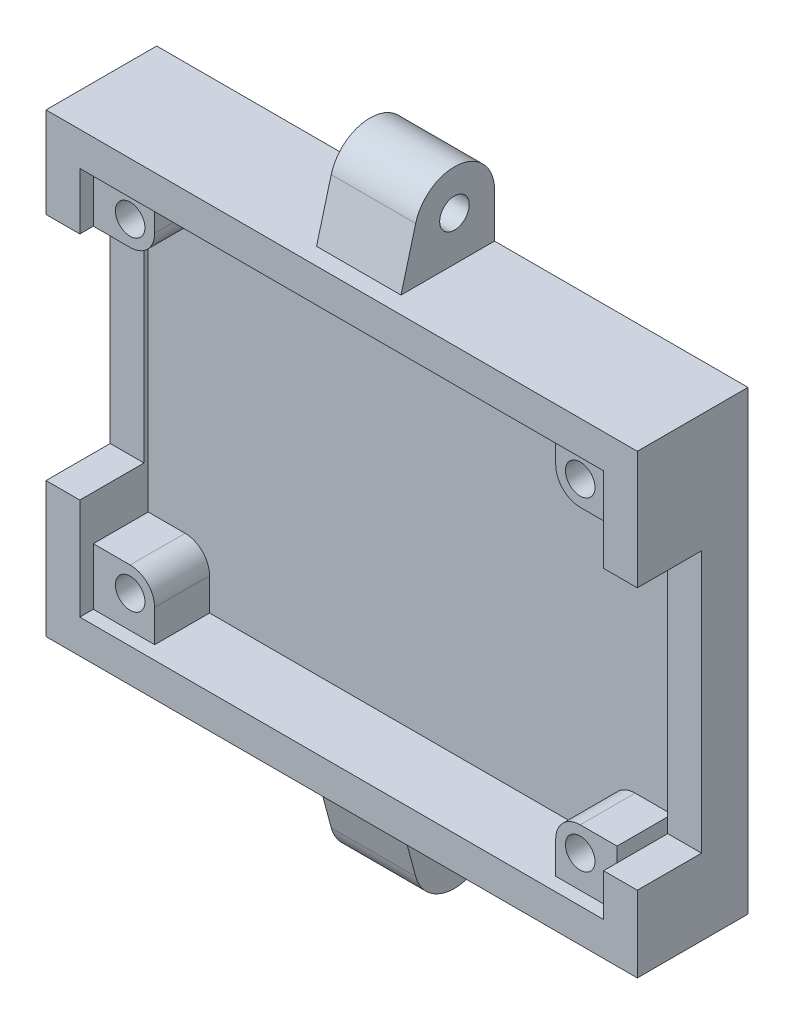
SolidWorks part; units mm, degrees
ref_plane "Front Plane" through (0, 0, 0) normal (0, 0, 1) x (1, 0, 0)
ref_plane "Top Plane" through (0, 0, 0) normal (0, 1, 0) x (1, 0, 0)
ref_plane "Right Plane" through (0, 0, 0) normal (1, 0, 0) x (0, 0, -1)
sketch "Sketch1" plane through (0, 0, 0) normal (0, 0, 1) x (1, 0, 0)
  line L0 (0, -55) -> (0, 55) construction
  line L1 (-31, -23) -> (31, -23)
  line L2 (-31, -23) -> (-31, 23)
  line L3 (-31, 23) -> (31, 23)
  line L4 (31, -23) -> (31, 23)
  line L5 (-31, -23) -> (31, 23) construction
  line L6 (-31, 23) -> (31, -23) construction
  line L7 (55, 0) -> (-55, 0) construction
  line L8 (-35, -27) -> (-35, 27)
  line L9 (-35, 27) -> (35, 27)
  line L10 (35, -27) -> (35, 27)
  line L11 (-35, -27) -> (35, -27)
  circle A0 centre (-26.6383, 19.175) radius 1.75
  circle A1 centre (26.6383, 19.175) radius 1.75
  circle A2 centre (-26.6383, -19.175) radius 1.75
  circle A3 centre (26.6383, -19.175) radius 1.75
  point P0 (0, 0)
  dimension "D1" = 53.2767
  dimension "D5" = 3.5
  dimension "D2" = 38.35
  dimension "D3" = 62
  dimension "D4" = 46
  dimension "D6" = 4
extrude "Boss-Extrude1" add sketch "Sketch1" along normal blind 5 contours L1 L4 L3 L2 A3 A1 A0 A2 region at (0, 0, 0)
extrude "Boss-Extrude2" add sketch "Sketch1<3>" along normal offset from surface (13.1 mm away) 8.1 contours L8 L11 L10 L9 L4 L1 L2 L3 region at (-34.1159, 0, 0) up to face at (28.3883, -19.175, 5) offset beyond the face yes
sketch "Sketch1<3>" plane through (0, 0, 0) normal (0, 0, 1) x (1, 0, 0) same geometry as "Sketch1"
sketch "Sketch2" plane through (0, 0, 5) normal (0, 0, 1) x (1, 0, 0)
  line L1 (-9.8333, 23) -> (2.8667, 23)
  line L2 (-9.8333, 23) -> (-9.8333, 19)
  line L3 (-9.8333, 19) -> (2.8667, 19)
  line L4 (2.8667, 23) -> (2.8667, 19)
  line L7 (-31, 23) -> (31, 23) construction
  line L8 (-31, -23) -> (-31, 23) construction
  point P4 (-8.8333, 22.25)
  dimension "D1" = 4
  dimension "D2" = 12.7
  dimension "D3" = 21.1667
extrude "Cut-Extrude1" cut sketch "Sketch2" against normal blind 4
sketch "Sketch3" plane through (0, 0, 5) normal (0, 0, 1) x (1, 0, 0)
  line L0 (-23.7383, 19.175) -> (-23.7383, 23)
  line L1 (-31, 23) -> (-9.8333, 23) construction
  line L2 (-23.7383, 23) -> (-31, 23)
  line L3 (-31, 23) -> (-31, 16.275)
  line L4 (-31, -23) -> (-31, 23) construction
  line L5 (-31, 16.275) -> (-26.6383, 16.275)
  line L7 (55, 0) -> (-55, 0) construction
  line L8 (-31, -16.275) -> (-26.6383, -16.275)
  line L9 (-31, -23) -> (-31, -16.275)
  line L10 (-23.7383, -23) -> (-31, -23)
  line L11 (-23.7383, -19.175) -> (-23.7383, -23)
  line L12 (0, -55) -> (0, 55) construction
  line L13 (31, -23) -> (31, -16.275)
  line L14 (23.7383, -23) -> (31, -23)
  line L15 (23.7383, -19.175) -> (23.7383, -23)
  line L16 (31, -16.275) -> (26.6383, -16.275)
  line L17 (31, 16.275) -> (26.6383, 16.275)
  line L18 (31, 23) -> (31, 16.275)
  line L19 (23.7383, 23) -> (31, 23)
  line L20 (23.7383, 19.175) -> (23.7383, 23)
  arc A0 (-26.6383, 16.275) -> (-23.7383, 19.175) centre (-26.6383, 19.175) ccw
  arc A4 (-26.6383, -16.275) -> (-23.7383, -19.175) centre (-26.6383, -19.175) cw
  arc A5 (26.6383, -16.275) -> (23.7383, -19.175) centre (26.6383, -19.175) ccw
  arc A6 (26.6383, 16.275) -> (23.7383, 19.175) centre (26.6383, 19.175) cw
  circle A7 centre (-26.6383, -19.175) radius 1.75 construction
  circle A8 centre (26.6383, -19.175) radius 1.75 construction
  circle A9 centre (26.6383, 19.175) radius 1.75 construction
  circle A10 centre (-26.6383, 19.175) radius 1.75 construction
  circle A11 centre (-26.6383, -19.175) radius 1.75
  circle A12 centre (26.6383, -19.175) radius 1.75
  circle A13 centre (26.6383, 19.175) radius 1.75
  circle A14 centre (-26.6383, 19.175) radius 1.75
  dimension "D1" = 5.8
extrude "Boss-Extrude3" add sketch "Sketch3" along normal blind 6.5
sketch "Sketch4" plane through (0, 0, 13.1) normal (0, 0, 1) x (1, 0, 0)
  line L0 (-35, -27) -> (-35, 27) construction
  line L1 (-31, 16.275) -> (-35, 16.275)
  line L2 (-31, 16.275) -> (-31, -11)
  line L3 (-31, -11) -> (-35, -11)
  line L4 (-35, 16.275) -> (-35, -11)
  line L11 (-23.7383, 23) -> (-31, 23) construction
  line L12 (31, -16.275) -> (31, 16.275) construction
  line L13 (31, -18) -> (35, -18)
  line L14 (31, -18) -> (31, 13)
  line L15 (31, 13) -> (35, 13)
  line L16 (35, -18) -> (35, 13)
  line L17 (35, -27) -> (35, 27) construction
  line L19 (-31, -23) -> (31, -23) construction
  line L20 (23.7383, -23) -> (31, -23) construction
  dimension "D1" = 34
  dimension "D2" = 5
  dimension "D3" = 36
extrude "Cut-Extrude2" cut sketch "Sketch4" against normal offset from surface (7.6 mm away) 6 up to face at (-27.1029, 19.4249, 11.5)
sketch "Sketch5" plane through (0, 0, 0) normal (1, 0, 0) x (0, 0, -1)
  line L0 (-11.0743, 27) -> (-9.3381, 33.4794)
  line L1 (-13.1, 27) -> (0, 27) construction
  line L2 (0, 32.25) -> (0, 27)
  line L3 (0, 27) -> (-11.0743, 27)
  line L4 (55, 0) -> (-55, 0) construction
  line L5 (0, -32.25) -> (0, -27)
  line L6 (-11.0743, -27) -> (-9.3381, -33.4794)
  line L7 (0, -27) -> (-11.0743, -27)
  arc A0 (-9.3381, 33.4794) -> (0, 32.25) centre (-4.75, 32.25) cw
  circle A1 centre (-4.75, 32.25) radius 1.75
  circle A2 centre (-4.75, -32.25) radius 1.75
  arc A3 (-9.3381, -33.4794) -> (0, -32.25) centre (-4.75, -32.25) ccw
  point P6 (0, 0)
  point P9 (-4.75, 30.5)
  dimension "D1" = 3.5
  dimension "D2" = 3
  dimension "D3" = 75
  dimension "D4" = 3.5
extrude "Boss-Extrude4" add sketch "Sketch5" along normal mid plane 10
